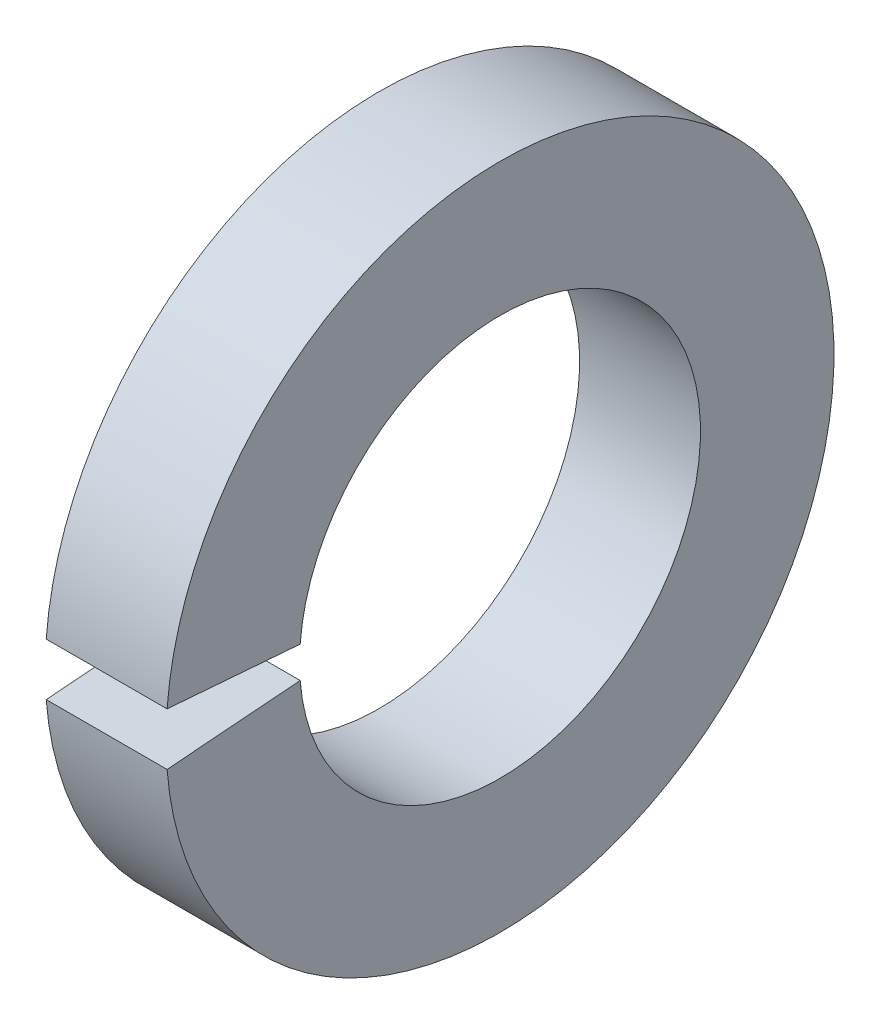
SolidWorks part; units mm, degrees
ref_plane "Plane1" through (0, 0, 0) normal (0, 0, 1) x (1, 0, 0)
ref_plane "Plane2" through (0, 0, 0) normal (0, 1, 0) x (1, 0, 0)
ref_plane "Plane3" through (0, 0, 0) normal (1, 0, 0) x (0, 0, -1)
sketch "Sketch1" plane through (0, 0, 0) normal (0, 0, 1) x (1, 0, 0)
  line L0 (-34.925, 0) -> (9.525, 0) construction
  line L1 (0, 12.8905) -> (0, 21.4757)
  line L2 (0, 21.4757) -> (-7.7724, 21.4757)
  line L3 (-7.7724, 21.4757) -> (-7.7724, 12.8905)
  line L4 (-7.7724, 12.8905) -> (0, 12.8905)
  dimension "Thickness" = 7.7724
revolve "Base-Revolve" add sketch "Sketch1" angle 360 about L0
sketch "Sketch2" plane through (0, 0, 0) normal (-1, 0, 0) x (0, -1, 0)
  line L0 (0, 0) -> (1.7187, 21.8377)
  line L1 (0, -3.175) -> (0, 12.7) construction
  line L2 (0, 0) -> (-1.7187, 21.8377)
  arc A0 (1.7187, 21.8377) -> (-1.7187, 21.8377) centre (0, 0) ccw
  dimension "D1" = 21.9052
extrude "Gap" cut sketch "Sketch2" along normal through all
equation "\"D1@Sketch2\" = \"Outside_dia@Sketch1\" * 0.51"
